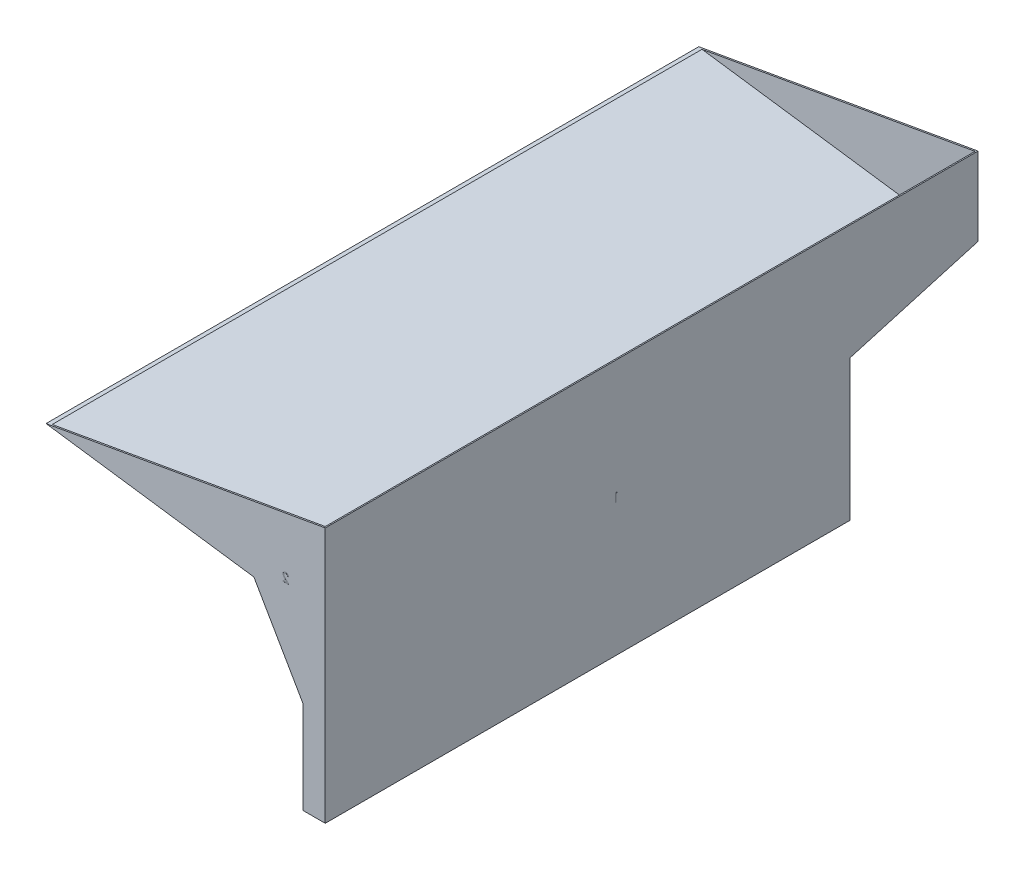
SolidWorks part; units mm, degrees
material "Melamine"
ref_plane "Front Plane" through (0, 0, 0) normal (0, 0, 1) x (1, 0, 0)
ref_plane "Top Plane" through (0, 0, 0) normal (0, 1, 0) x (1, 0, 0)
ref_plane "Right Plane" through (0, 0, 0) normal (1, 0, 0) x (0, 0, -1)
other "Center of Mass"
sketch "Sketch2" plane through (0, 0, 0) normal (0, 0, 1) x (1, 0, 0)
  line L0 (0, 0) -> (-105, 181.8653)
  line L1 (-105, 181.8653) -> (-551.9888, 244.1441)
  line L2 (-551.9888, 244.1441) -> (48.35, 350)
  line L3 (48.35, 350) -> (48.35, -200)
  line L4 (48.35, -200) -> (0, -200)
  line L5 (0, -200) -> (0, 0)
  dimension "D1" = 150
  dimension "D2" = 609.6
  dimension "D3" = 550
  dimension "D4" = 200
  dimension "D5" = 48.35
  dimension "D6" = 210
  dimension "D7" = 280
extrude "Boss-Extrude1" add sketch "Sketch2" along normal mid plane 1403.35
shell "Shell1" thickness 3.175 removed face at (-251.8194, 297.072, 0)
sketch "Sketch3" plane through (0, 0, 701.675) normal (0, 0, 1) x (1, 0, 0)
  line L1 (3.175, -187.3) -> (45.175, -187.3)
  line L2 (3.175, -187.3) -> (3.175, 102.7)
  line L3 (3.175, 102.7) -> (45.175, 102.7)
  line L4 (45.175, -187.3) -> (45.175, 102.7)
  line L6 (0, -200) -> (48.35, -200) construction
  point P6 (24.175, -200)
  point P7 (24.175, -187.3)
  dimension "D1" = 42
  dimension "D2" = 12.7
  dimension "D3" = 290
extrude "Cut-Extrude1" cut sketch "Sketch3" against normal blind 20
sketch "Sketch7" plane through (0, 0, 0) normal (-1, 0, 0) x (0, 0, 1)
  line L1 (701.675, -200) -> (426.675, -200)
  line L2 (701.675, -200) -> (701.675, 102.7)
  line L3 (701.675, 102.7) -> (426.675, 102.7)
  line L4 (426.675, -200) -> (426.675, 102.7)
  dimension "D1" = 275
  dimension "D2" = 302.7
extrude "Cut-Extrude5" cut sketch "Sketch7" against normal mid plane 200
sketch "Sketch9" plane through (48.35, 0, 0) normal (1, 0, 0) x (0, 0, -1)
  line L0 (-701.675, 102.7) -> (-701.675, 350) construction
  line L1 (-426.675, 102.7) -> (-701.675, 102.7)
  line L2 (-426.675, 102.7) -> (-426.675, 181.7)
  line L3 (-426.675, 181.7) -> (-701.675, 181.7)
  line L4 (-701.675, 102.7) -> (-701.675, 181.7)
  line L5 (-701.675, 181.7) -> (-426.675, 102.7)
  line M2 (-701.675, 102.7) -> (-426.675, 102.7)
  line M7 (-701.675, 350) -> (-701.675, 102.7)
  dimension "D1" = 79
extrude "Cut-Extrude7" cut sketch "Sketch9" against normal through all contours L5 M7 M2 region at (48.35, 129.0333, 610.0083)
sketch "Sketch11" plane through (0, -18.3572, 5.2735) normal (0, -0.9611, 0.2761) x (1, 0, 0)
  line L0 (48.35, 724.5674) -> (48.35, 438.445)
  line L1 (48.35, 438.445) -> (-59.2939, 438.445)
  line L2 (-59.2939, 438.445) -> (-104.9045, 724.5674)
  line L3 (-104.9045, 724.5674) -> (48.35, 724.5674)
extrude "Boss-Extrude3" add sketch "Sketch11" against normal blind 6.35
sketch "Sketch12" plane through (3.175, 0, 0) normal (1, 0, 0) x (0, 0, -1)
  line L0 (-426.675, -196.825) -> (688.975, -79.5655)
  line L1 (688.975, -79.5655) -> (688.975, -82.7405)
  line L2 (-396.4669, -196.825) -> (-426.675, -196.825)
  line L3 (701.675, -200) -> (701.675, 350) construction
  line L4 (688.975, -82.7405) -> (-396.4669, -196.825)
  line L5 (-396.4669, -196.825) -> (-396.4669, -193.65)
  line M5 (-426.675, -196.825) -> (698.5, -196.825)
  dimension "D1" = 3.175
  dimension "D2" = 12.7
  dimension "D3" = 6
  dimension "D4" = 3.175
  dimension "D5" = 3.175
extrude "Boss-Extrude4" add sketch "Sketch12" along normal up to surface (42 mm away) contours L5 L4 L1 L0 | L5 L0 M5 region at (3.175, -195.7667, 406.5363) region at (3.175, -138.1952, -146.2541) up to face at (45.175, 100.5897, 182.6102)
chamfer "Chamfer1" distance 6.35 angle 45 1 edges at (24.175, -196.825, 426.675) first distance on face at (24.175, -138.1952, -131.15)
sketch "Sketch14" plane through (48.35, 0, 0) normal (1, 0, 0) x (0, 0, -1)
  line L0 (-426.675, 102.7) -> (-426.675, -200) construction
  line L1 (-426.675, -200) -> (701.675, -200) construction
  text T0 "1" font "Century Gothic" height in points 72
  dimension "D1" = 496.5296
  dimension "D2" = 284.9328
extrude "Cut-Extrude8" cut sketch "Sketch14" against normal blind 0.1
sketch "Sketch15" plane through (0, 0, -701.675) normal (0, 0, -1) x (-1, 0, 0)
  text T0 "2" font "Century Gothic" height in points 72
extrude "Cut-Extrude9" cut sketch "Sketch15" against normal blind 0.1
sketch "Sketch16" plane through (22.8572, 164.0511, 0) normal (-0.138, -0.9904, 0) x (0.9904, -0.138, 0)
  text T0 "3" font "Century Gothic" height in points 72
extrude "Cut-Extrude10" cut sketch "Sketch16" against normal blind 0.1
sketch "Sketch17" plane through (0, 0, 0) normal (-0.866, -0.5, 0) x (0, 0, 1)
  text T0 "4" font "Century Gothic" height in points 72
extrude "Cut-Extrude11" cut sketch "Sketch17" against normal blind 0.1
sketch "Sketch18" plane through (0, 0, 0) normal (-1, 0, 0) x (0, 0, 1)
  text T0 "5" font "Century Gothic" height in points 72
extrude "Cut-Extrude12" cut sketch "Sketch18" against normal blind 0.1
sketch "Sketch19" plane through (0, -200, 0) normal (0, -1, 0) x (1, 0, 0)
  text T0 "6" font "Century Gothic" height in points 72
extrude "Cut-Extrude13" cut sketch "Sketch19" against normal blind 0.1
sketch "Sketch20" plane through (0, -18.3572, 5.2735) normal (0, -0.9611, 0.2761) x (1, 0, 0)
  text T0 "7" font "Century Gothic" height in points 72
extrude "Cut-Extrude14" cut sketch "Sketch20" against normal blind 0.1
sketch "Sketch21" plane through (0, 0, 701.675) normal (0, 0, 1) x (1, 0, 0)
  text T0 "8" font "Century Gothic" height in points 72
extrude "Cut-Extrude15" cut sketch "Sketch21" against normal blind 0.1
mirror "Mirror1" about plane through (0, 0, -701.675) normal (0, 0, 1) of bodies 122
sketch "Sketch22" plane through (0, 0, 0) normal (-1, 0, 0) x (0, 0, 1)
  line L5 (-701.675, -200) -> (1024.7166, -200)
  line L6 (-701.675, -200) -> (-701.675, 602.0407)
  line L7 (-701.675, 602.0407) -> (1024.7166, 602.0407)
  line L8 (1024.7166, -200) -> (1024.7166, 602.0407)
extrude "Cut-Extrude16" cut sketch "Sketch22" against normal through all both and the other way through all
